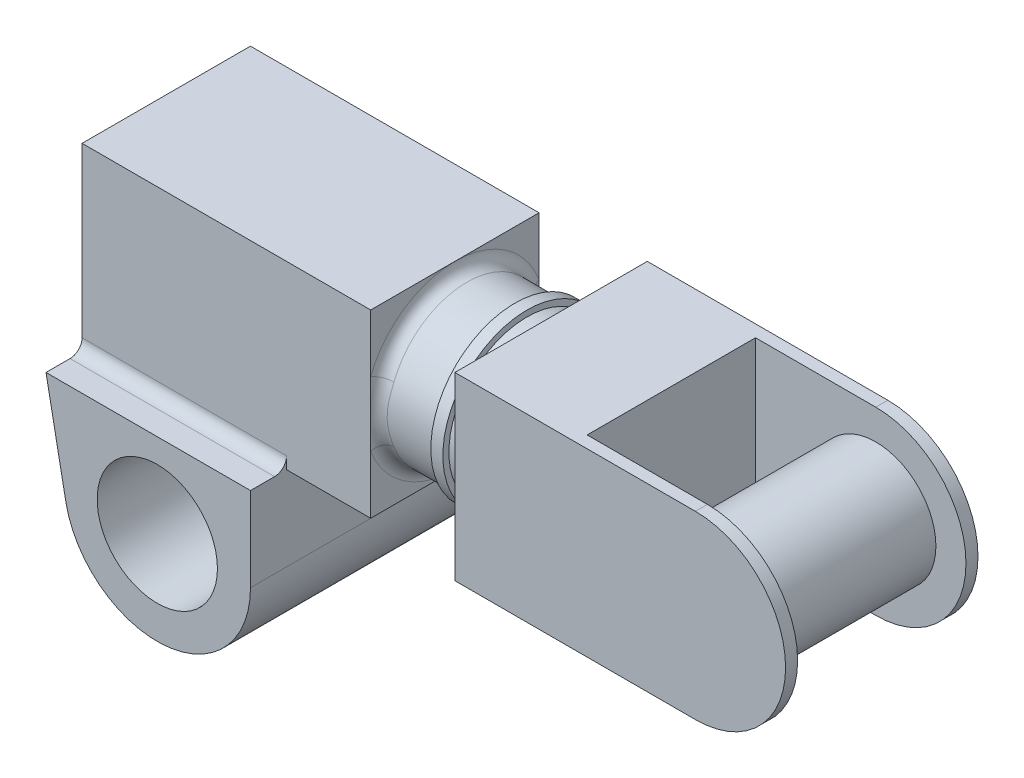
SolidWorks part; units mm, degrees
ref_plane "Front Plane" through (0, 0, 0) normal (0, 0, 1) x (1, 0, 0)
ref_plane "Top Plane" through (0, 0, 0) normal (0, 1, 0) x (1, 0, 0)
ref_plane "Right Plane" through (0, 0, 0) normal (1, 0, 0) x (0, 0, -1)
sketch "Sketch1" plane through (0, 0, 0) normal (1, 0, 0) x (0, 0, -1)
  line L1 (-70, -75) -> (70, -75)
  line L2 (-70, -75) -> (-70, 75)
  line L3 (-70, 75) -> (70, 75)
  line L4 (70, -75) -> (70, 75)
  line L5 (-70, -75) -> (70, 75) construction
  line L6 (-70, 75) -> (70, -75) construction
  point P0 (0, 0)
  dimension "D1" = 150
  dimension "D2" = 140
extrude "Boss-Extrude1" add sketch "Sketch1" along normal blind 240
sketch "Sketch2" plane through (240, 0, 0) normal (1, 0, 0) x (0, 0, -1)
  circle A0 centre (0, 0) radius 65
  dimension "D1" = 130
extrude "Boss-Extrude2" add sketch "Sketch2" along normal blind 50
sketch "Sketch3" plane through (290, 0, 0) normal (1, 0, 0) x (0, 0, -1)
  circle A0 centre (0, 0) radius 70
  dimension "D1" = 140
extrude "Boss-Extrude3" add sketch "Sketch3" along normal blind 10
sketch "Sketch4" plane through (0, 0, 0) normal (0, 0, 1) x (1, 0, 0)
  line L0 (0, -75) -> (16.5223, -160)
  line L1 (0, -75) -> (170.0569, -75)
  line L2 (0, 75) -> (0, -75) construction
  line L3 (170.0569, -145) -> (170.0569, -75)
  line L4 (240, -75) -> (0, -75) construction
  arc A0 (16.4398, -159.5753) -> (170.0569, -145) centre (92.5569, -145) ccw
  circle A1 centre (92.5569, -145) radius 50
  dimension "D1" = 191
  dimension "D2" = 100
  dimension "D4" = 155
  dimension "D3" = 85
  dimension "D5" = 70
extrude "Boss-Extrude4" add sketch "Sketch4" along normal mid plane 200 contours L0 A0 L3 L1 A1 region at (85.0284, -77.2511, 0)
fillet "Fillet3" radius 10 3 edges at (85.0284, -75, 70) (240, 0, -65) (85.0284, -75, -70)
sketch "Sketch6" plane through (300, 0, 0) normal (1, 0, 0) x (0, 0, -1)
  circle A0 centre (0, 0) radius 65
  dimension "D1" = 130
extrude "Boss-Extrude5" add sketch "Sketch6" along normal blind 20
sketch "Sketch7" plane through (0, 0, 0) normal (0, 0, 1) x (1, 0, 0)
  line L0 (520, 75) -> (320, 75)
  line L1 (320, 75) -> (320, -75)
  line L2 (320, -75) -> (520, -75)
  line L3 (320, -65) -> (320, 65) construction
  arc A0 (520, -75) -> (520, 75) centre (520, 0) ccw
  dimension "D1" = 150
  dimension "D2" = 200
extrude "Boss-Extrude6" add sketch "Sketch7" along normal mid plane 160
sketch "Sketch8" plane through (0, 0, 0) normal (0, 0, 1) x (1, 0, 0)
  line L0 (520, 75) -> (420, 75)
  line L1 (520, 75) -> (320, 75) construction
  line L2 (420, 75) -> (420, -75)
  line L3 (320, -75) -> (520, -75) construction
  line L4 (420, -75) -> (520, -75)
  arc A0 (520, -75) -> (520, 75) centre (520, 0) ccw construction
  arc A1 (520, -75) -> (520, 75) centre (520, 0) ccw
extrude "Cut-Extrude1" cut sketch "Sketch8" against normal mid plane 140
sketch "Sketch9" plane through (0, 0, -70) normal (0, 0, 1) x (1, 0, 0)
  circle A0 centre (520, 0) radius 50
  dimension "D1" = 100
extrude "Boss-Extrude7" add sketch "Sketch9" along normal blind 140
